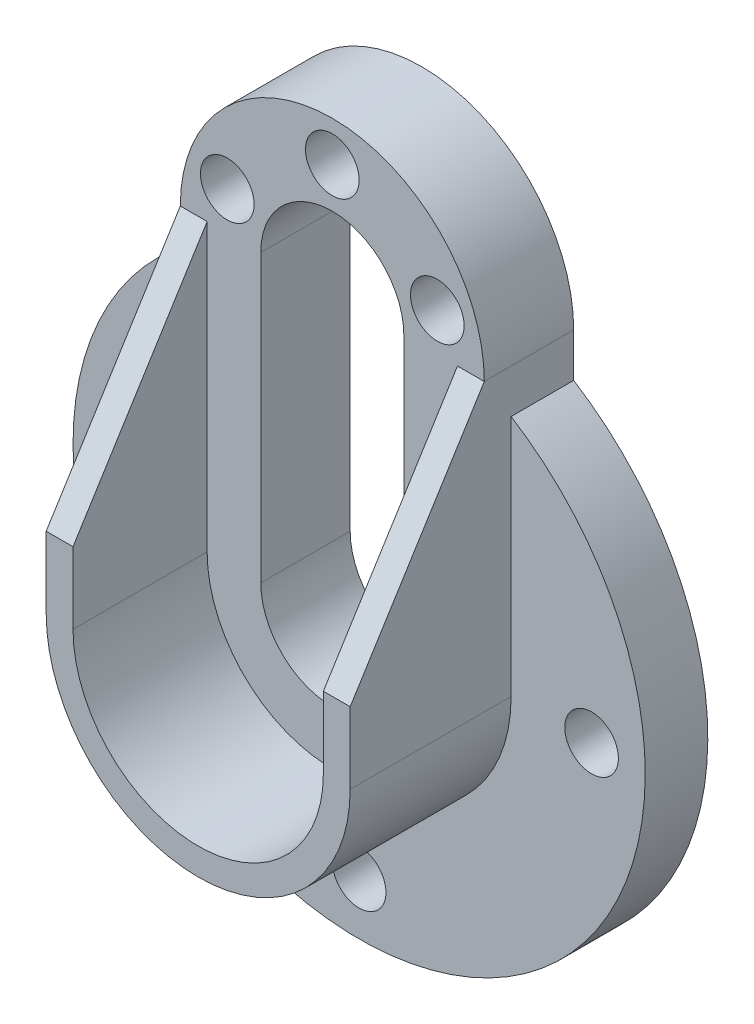
SolidWorks part; units mm, degrees
ref_plane "Front Plane" through (0, 0, 0) normal (0, 0, 1) x (1, 0, 0)
ref_plane "Top Plane" through (0, 0, 0) normal (0, 1, 0) x (1, 0, 0)
ref_plane "Right Plane" through (0, 0, 0) normal (1, 0, 0) x (0, 0, -1)
sketch "Sketch1" plane through (0, 0, 0) normal (0, 0, 1) x (1, 0, 0)
  line L0 (0, 63.5) -> (0, 70.6438) construction
  line L1 (26.9875, 0) -> (26.9875, 50.8)
  line L2 (-26.9875, 50.8) -> (-26.9875, 0)
  line L3 (0, 50.8) -> (-26.9875, 50.8) construction
  line L4 (-12.7, 50.8) -> (-12.7, 0)
  line L5 (12.7, 50.8) -> (12.7, 0)
  line L6 (-18.647, 57.587) -> (-11.9341, 55.1437) construction
  line L7 (-18.647, 57.587) -> (-25.36, 60.0303) construction
  line L8 (0, 70.6438) -> (0, 77.7875) construction
  line L9 (-22.225, 0) -> (-22.225, 50.8)
  line L10 (-22.225, 50.8) -> (-26.9875, 50.8)
  line L11 (22.225, 0) -> (22.225, 50.8)
  line L12 (22.225, 50.8) -> (26.9875, 50.8)
  arc A0 (-26.9875, 43.0385) -> (26.9875, 43.0385) centre (0, 0) ccw
  circle A1 centre (41.275, 0) radius 4.7625
  circle A2 centre (0, -41.275) radius 4.7625
  circle A3 centre (-41.275, 0) radius 4.7625
  arc A4 (-26.9875, 0) -> (26.9875, 0) centre (0, 0) ccw
  arc A5 (26.9875, 50.8) -> (-26.9875, 50.8) centre (0, 50.8) ccw
  arc A6 (12.7, 50.8) -> (-12.7, 50.8) centre (0, 50.8) ccw
  arc A7 (-12.7, 0) -> (12.7, 0) centre (0, 0) ccw
  circle A8 centre (-18.647, 57.587) radius 4.7625
  circle A9 centre (0, 70.6438) radius 4.7625
  circle A10 centre (18.647, 57.587) radius 4.7625
  arc A11 (-22.225, 0) -> (22.225, 0) centre (0, 0) ccw
  point P11 (0, 0)
  dimension "D1" = 101.6
  dimension "D2" = 9.525
  dimension "D3" = 41.275
  dimension "D5" = 41.275
  dimension "D6" = 53.975
  dimension "D8" = 12.7
  dimension "D9" = 9.525
  dimension "D11" = 9.525
  dimension "D12" = 44.45
  dimension "D7" = 50.8
  dimension "D10" = 20
  dimension "D4" = 3
extrude "Boss-Extrude1" add sketch "Sketch1" along normal blind 11.1125 contours A4 L2 A0 L1 A3 A2 A1 | A11 L9 L10 L2 A4 L1 L12 L11 | L9 A11 L11 L12 A5 L10 A7 L4 A6 L5 A8 A9 A10 region at (0, -26.0407, 0) region at (28.3705, 21.5193, 0) region at (24.6062, 51.9365, 0)
extrude "Boss-Extrude2" add sketch "Sketch1<3>" along normal blind 15.875 contours A11 L9 L10 L2 A4 L1 L12 L11 | L9 A11 L11 L12 A5 L10 A7 L4 A6 L5 A8 A9 A10 region at (0, -26.0407, 0) region at (24.6062, 51.9365, 0)
sketch "Sketch1<3>" plane through (0, 0, 0) normal (0, 0, 1) x (1, 0, 0) same geometry as "Sketch1"
extrude "Boss-Extrude3" add sketch "Sketch1<4>" along normal blind 39.6875 contours A11 L9 L10 L2 A4 L1 L12 L11 region at (0, -26.0407, 0)
sketch "Sketch1<4>" plane through (0, 0, 0) normal (0, 0, 1) x (1, 0, 0) same geometry as "Sketch1"
sketch "Sketch2" plane through (26.9875, 0, 0) normal (1, 0, 0) x (0, 0, -1)
  line L0 (-15.875, 50.8) -> (-39.6875, 12.7)
  line L1 (-39.6875, 0) -> (-39.6875, 50.8) construction
  line L3 (-39.6875, 12.7) -> (-39.6875, 50.8)
  line L4 (-39.6875, 50.8) -> (-15.875, 50.8)
  dimension "D1" = 12.7
extrude "Cut-Extrude1" cut sketch "Sketch2" against normal through all
